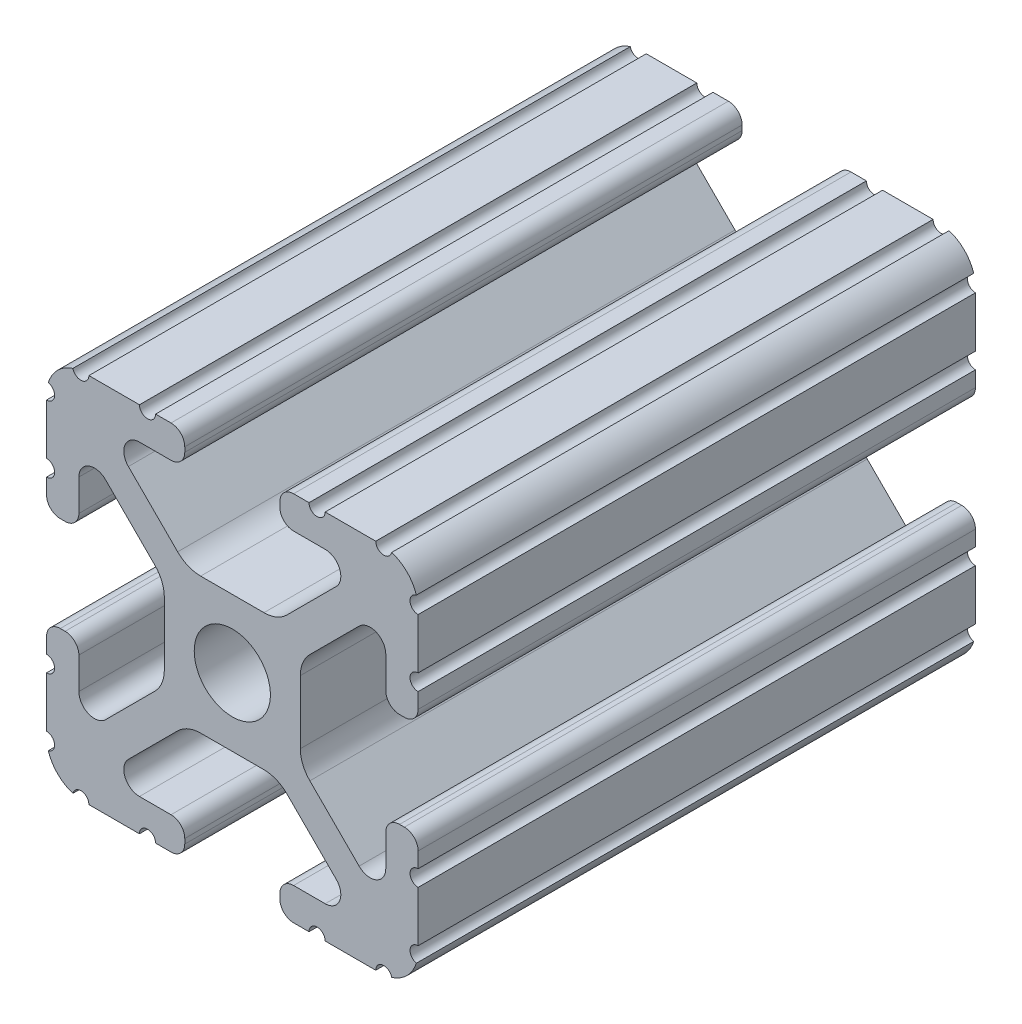
SolidWorks part; units mm, degrees
ref_plane "Front Plane" through (0, 0, 0) normal (0, 0, 1) x (1, 0, 0)
ref_plane "Top Plane" through (0, 0, 0) normal (0, 1, 0) x (1, 0, 0)
ref_plane "Right Plane" through (0, 0, 0) normal (1, 0, 0) x (0, 0, -1)
sketch "Sketch2" plane through (0, 0, 0) normal (0, 0, 1) x (1, 0, 0)
  line L0 (0, 12.7) -> (0, -12.7) construction
  line L1 (-12.7, 0) -> (12.7, 0) construction
  line L2 (3.2512, -12.7) -> (12.7, -12.7)
  line L3 (12.7, -12.7) -> (12.7, -3.2512)
  line L4 (3.2512, -12.7) -> (3.2512, -10.4902)
  line L5 (3.2512, -10.4902) -> (8.9276, -10.4902)
  line L6 (8.9276, -10.4902) -> (3.0856, -4.6482)
  line L7 (0, 0) -> (12.7, -12.7) construction
  line L8 (12.7, -3.2512) -> (10.4902, -3.2512)
  line L9 (10.4902, -3.2512) -> (10.4902, -8.9276)
  line L10 (10.4902, -8.9276) -> (4.6482, -3.0856)
  circle A0 centre (0, 0) radius 2.6035
  arc A1 (6.3485, -10.4902) -> (7.1039, -8.6665) centre (6.3485, -9.4219) ccw construction
  point P8 (0, -4.6482)
  dimension "Center Hole Diameter" = 5.207
  dimension "Rail Height" = 25.4
  dimension "Rail Width" = 25.4
  dimension "T-Slot Width" = 6.5024
  dimension "Slot Inner Width" = 14.8336
  dimension "Thickness" = 2.2098
  dimension "Slot Depth" = 5.842
  dimension "D1" = 2.2098
sketch "Sketch3" plane through (0, 0, 0) normal (1, 0, 0) x (0, 0, -1)
  line L0 (-76.2, -12.7) -> (76.2, -12.7) construction
  line L1 (-68.58, 0) -> (68.58, 0) construction
  dimension "Length" = 152.4
  dimension "D1" = 137.16
sketch "Sketch4" plane through (0, 0, 0) normal (0, 0, 1) x (1, 0, 0)
  line L0 (4.1904, -12.7) -> (10.1173, -12.7)
  line L1 (3.2512, -12.7) -> (12.7, -12.7) construction
  line L2 (3.2512, -12.7) -> (3.2512, -10.4902) construction
  line L3 (3.2512, -10.4902) -> (8.9276, -10.4902) construction
  line L4 (3.2512, -11.4294) -> (3.2512, -11.7608)
  line L5 (4.1904, -10.4902) -> (6.3485, -10.4902)
  line L6 (0, -4.6482) -> (2.164, -4.6482)
  line L7 (8.9276, -10.4902) -> (3.0856, -4.6482) construction
  line L8 (3.7373, -5.2999) -> (7.1039, -8.6665)
  line L9 (12.7, -12.7) -> (12.7, -3.2512) construction
  line L10 (10.4902, -8.9276) -> (4.6482, -3.0856) construction
  line L11 (10.4902, -3.2512) -> (10.4902, -8.9276) construction
  line L12 (10.4902, -6.3485) -> (10.4902, -4.1904)
  line L13 (12.7, -3.2512) -> (10.4902, -3.2512) construction
  line L14 (11.4294, -3.2512) -> (11.7608, -3.2512)
  line L15 (12.7, -4.1904) -> (12.7, -10.1173)
  line L16 (8.6665, -7.1039) -> (5.2999, -3.7373)
  line L17 (4.6482, 0) -> (4.6482, -2.164)
  line L18 (-12.7, 0) -> (12.7, 0) construction
  line L19 (0, -4.6482) -> (0, -2.6035)
  line L20 (0, 12.7) -> (0, -12.7) construction
  line L21 (4.6482, 0) -> (2.6035, 0)
  arc A0 (3.2512, -11.7608) -> (4.1904, -12.7) centre (4.1904, -11.7608) ccw
  arc A2 (3.2512, -11.4294) -> (4.1904, -10.4902) centre (4.1904, -11.4294) cw
  arc A3 (6.3485, -10.4902) -> (7.1039, -8.6665) centre (6.3485, -9.4219) ccw
  arc A4 (2.164, -4.6482) -> (3.7373, -5.2999) centre (2.164, -6.8732) cw
  arc A5 (10.1173, -12.7) -> (12.7, -10.1173) centre (10.1173, -10.1173) ccw
  arc A6 (8.6665, -7.1039) -> (10.4902, -6.3485) centre (9.4219, -6.3485) ccw
  arc A7 (10.4902, -4.1904) -> (11.4294, -3.2512) centre (11.4294, -4.1904) cw
  arc A8 (11.7608, -3.2512) -> (12.7, -4.1904) centre (11.7608, -4.1904) cw
  arc A9 (5.2999, -3.7373) -> (4.6482, -2.164) centre (6.8732, -2.164) cw
  circle A10 centre (0, 0) radius 2.6035 construction
  arc A11 (0, -2.6035) -> (2.6035, 0) centre (0, 0) ccw
  dimension "D1" = 2.5827
  dimension "D2" = 2.225
  dimension "D3" = 0.9392
extrude "Boss-Extrude1" add sketch "Sketch4" along normal mid plane 152.4
sketch "Sketch5" plane through (0, 0, 0) normal (0, 0, 1) x (1, 0, 0)
  line L0 (3.2512, -12.7) -> (12.7, -12.7) construction
  line L1 (4.1904, -10.4902) -> (6.3485, -10.4902) construction
  line L3 (0, 0) -> (12.7, -12.7) construction
  line L4 (6.3485, -10.4902) -> (6.3485, -12.7) construction
  line L5 (8.9276, -10.4902) -> (3.0856, -4.6482) construction
  circle A0 centre (10.3562, -12.7) radius 0.5524
  circle A1 centre (5.796, -12.7) radius 0.5524
  circle A2 centre (12.7, -10.3562) radius 0.5524
  circle A3 centre (12.7, -5.796) radius 0.5524
  point P10 (5.2694, -10.4902)
  point P12 (9.4219, -6.3485)
  dimension "D1" = 1.1049
extrude "Cut-Extrude1" cut sketch "Sketch5" against normal through all both and the other way through all
mirror "Mirror1" about plane through (0, 0, 0) normal (1, 0, 0) of bodies 137 134
mirror "Mirror2" about plane through (0, 0, 0) normal (0, 1, 0) of bodies 135
ref_plane "Plane1" through (0, 0, 0) normal (0, 0, -1) x (-1, 0, 0)
sketch "Sketch6" plane through (0, 0, 0) normal (0, 0, -1) x (-1, 0, 0)
  line L0 (-12.7, 9.8037) -> (-12.7, 6.3485) construction
  line L1 (-12.7, 12.7) -> (12.7, 12.7)
  line L2 (-12.7, 12.7) -> (-12.7, -12.7)
  line L3 (-12.7, -12.7) -> (12.7, -12.7)
  line L4 (12.7, 12.7) -> (12.7, -12.7)
  line L5 (12.7, 9.8037) -> (12.7, 6.3485) construction
  line L6 (-6.3485, 12.7) -> (-9.8037, 12.7) construction
  line L7 (-6.3485, -12.7) -> (-9.8037, -12.7) construction
extrude "Cut-Extrude2" cut sketch "Sketch6" against normal through all
ref_plane "Plane2" through (0, 0, -38.1) normal (0, 0, -1) x (-1, 0, 0)
sketch "Sketch7" plane through (0, 0, -38.1) normal (0, 0, -1) x (-1, 0, 0)
  line L0 (-12.7, -12.7) -> (12.7, -12.7) construction
  line L1 (12.7, 12.7) -> (12.7, -12.7) construction
  line L2 (-12.7, 12.7) -> (12.7, 12.7) construction
  line L3 (-12.7, 12.7) -> (-12.7, -12.7) construction
  line L4 (-12.7, -12.7) -> (12.7, -12.7)
  line L5 (12.7, 12.7) -> (12.7, -12.7)
  line L6 (-12.7, 12.7) -> (12.7, 12.7)
  line L7 (-12.7, 12.7) -> (-12.7, -12.7)
extrude "Cut-Extrude3" cut sketch "Sketch7" against normal through all
sketch "Sketch9" plane through (-12.7, 0, 0) normal (-1, 0, 0) x (0, 0, 1)
  line L0 (-38.1, -12.58) -> (-38.1, 12.7) construction
  line L1 (-38.1, 0.06) -> (-50.8, 0.06) construction
  circle A0 centre (-50.8, 0.06) radius 3.2639
  dimension "D1" = 6.5278
  dimension "D2" = 12.7
extrude "Cut-Extrude4" cut sketch "Sketch9" against normal through all
equation "\"D1@Boss-Extrude1\"=\"Length@Sketch3\""
equation "\"D1@Sketch2\"=\"Thickness@Sketch2\""
equation "\"D2@Sketch4\"=\"Slot Inner Width@Sketch2\"*0.15"
equation "\"D1@Sketch4\"=\"D3@Sketch4\"*2.75"
equation "\"D3@Sketch4\"=\"Thickness@Sketch2\"*0.425"
equation "\"D1@Sketch5\"=\"Thickness@Sketch2\"*0.5"
equation "\"D1@Sketch3\"=\"Length@Sketch3\"*0.9"
